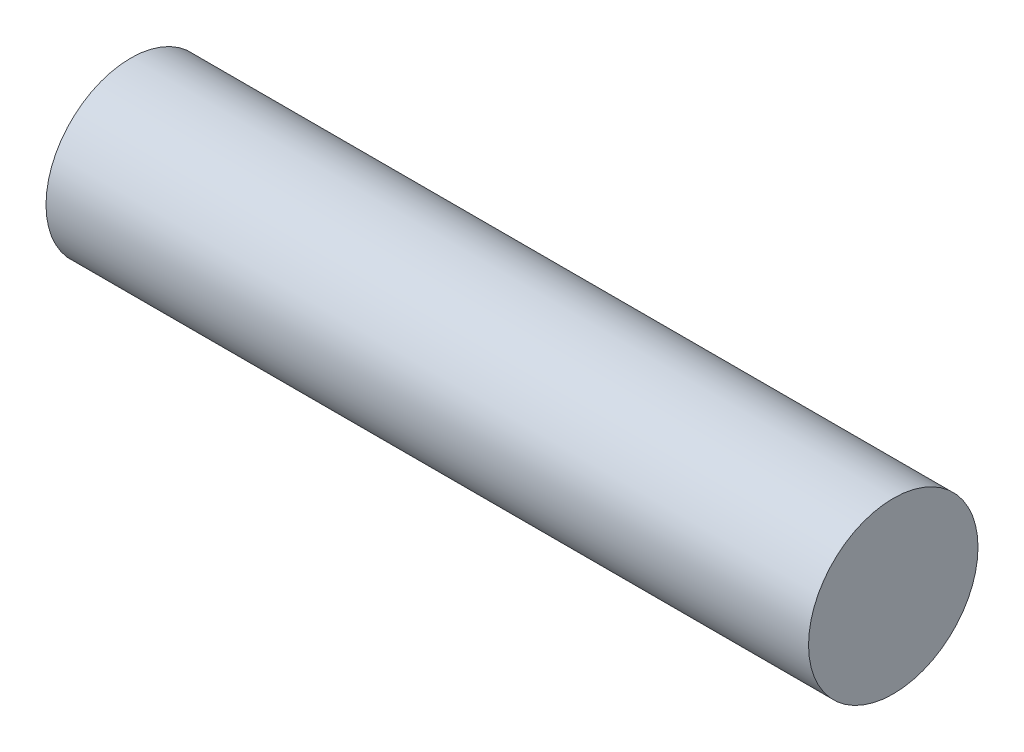
SolidWorks part; units mm, degrees
ref_plane "前视基准面" through (0, 0, 0) normal (0, 0, 1) x (1, 0, 0)
ref_plane "上视基准面" through (0, 0, 0) normal (0, 1, 0) x (1, 0, 0)
ref_plane "右视基准面" through (0, 0, 0) normal (1, 0, 0) x (0, 0, -1)
other "Configuration Table"
sketch "草图1" plane through (0, 0, 0) normal (0, 0, 1) x (1, 0, 0)
  circle A0 centre (0, 0) radius 38
  circle A1 centre (0, 0) radius 33 construction
  circle A2 centre (0, 33) radius 2.5
  circle A3 centre (0, 0) radius 27.5
  dimension "D1" = 76
  dimension "D2" = 66
  dimension "D3" = 5
  dimension "D4" = 55
extrude "凸台-拉伸1" add sketch "草图1" along normal blind 5
sketch "草图2" plane through (0, 0, 0) normal (0, 0, -1) x (-1, 0, 0)
  line L0 (-30.995, 21.9843) -> (-73.1164, -37.4014)
  line L1 (-73.1164, -37.4014) -> (-73.1164, -52.3924)
  line L2 (-73.1164, -52.3924) -> (46.8836, -52.3924)
  line L3 (46.8836, -52.3924) -> (37.521, 6.0146)
  circle A0 centre (0, 0) radius 38 construction
  arc A1 (-30.995, 21.9843) -> (37.521, 6.0146) centre (0, 0) ccw
  dimension "D1" = 120
extrude "凸台-拉伸2" add sketch "草图2" against normal blind 20
fillet "圆角2" radius 2.5 2 edges at (30.995, 21.9843, 12.5) (-37.521, 6.0146, 12.5)
fillet "圆角3" radius 10 1 edges at (-46.8836, -52.3924, 10)
fillet "圆角4" radius 5 2 edges at (73.1164, -52.3924, 10) (73.1164, -37.4014, 10)
sketch "草图3" plane through (0, -52.3924, 0) normal (0, -1, 0) x (1, 0, 0)
  line L0 (68.1164, 0) -> (68.1164, 20) construction
  line L1 (-35.153, 20) -> (68.1164, 20)
  line L2 (-35.153, 20) -> (-35.153, 10)
  line L3 (-35.153, 10) -> (68.1164, 10)
  line L4 (68.1164, 20) -> (68.1164, 10)
revolve "旋转1" add sketch "草图3" angle 180 about L3
fillet "圆角6" radius 20 2 edges at (68.1164, -52.3924, 10) (-35.153, -52.3924, 10)
ref_plane "基准面1" through (0, 0, 10) normal (0, 0, 1) x (1, 0, 0)
sketch "草图4" plane through (0, 0, 0) normal (1, 0, 0) x (0, 0, -1)
  line L0 (-10, -52.3924) -> (-10, 0) construction
  line L1 (-10, 0) -> (0, 0) construction
  line L3 (-20, 52.3924) -> (0, 52.3924)
  line L4 (-20, 52.3924) -> (-20, -52.3924)
  line L5 (-20, -52.3924) -> (0, -52.3924) construction
  line L6 (0, 52.3924) -> (0, -52.3924)
  line L7 (-20, 52.3924) -> (0, -52.3924) construction
  line L8 (-20, -52.3924) -> (0, 52.3924) construction
  arc A0 (0, -52.3924) -> (-20, -52.3924) centre (-10, -52.3924) ccw
extrude "切除-拉伸1" cut sketch "草图4" against normal up to next and the other way up to next
ref_plane "基准面2" through (-30, 0, 0) normal (1, 0, 0) x (0, 0, -1)
sketch "草图5" plane through (-30, 0, 0) normal (1, 0, 0) x (0, 0, -1)
  circle A0 centre (-10, -52.3924) radius 13.5739
extrude "切除-拉伸2" cut sketch "草图5" against normal blind 27
ref_plane "基准面3" through (60, 0, 0) normal (1, 0, 0) x (0, 0, -1)
sketch "草图6" plane through (60, 0, 0) normal (1, 0, 0) x (0, 0, -1)
  circle A0 centre (-10, -52.3924) radius 12.2887
extrude "切除-拉伸3" cut sketch "草图6" along normal up to next
